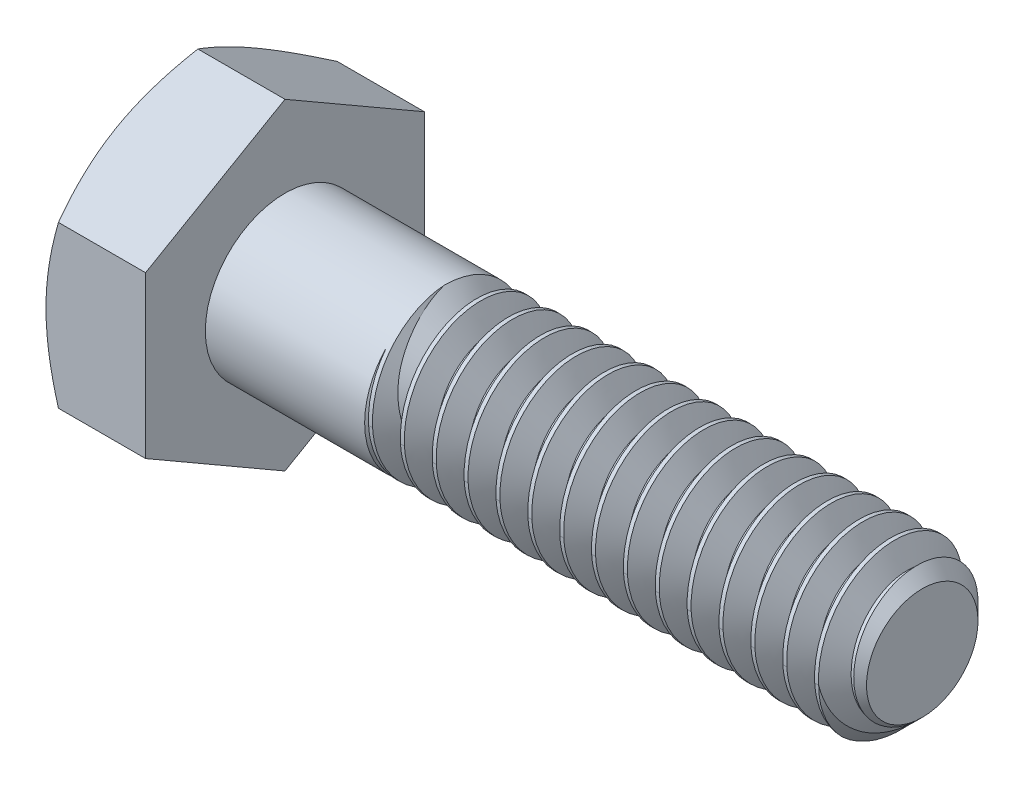
SolidWorks part; units mm, degrees
ref_plane "Front Plane" through (0, 0, 0) normal (0, 0, 1) x (1, 0, 0)
ref_plane "Top Plane" through (0, 0, 0) normal (0, 1, 0) x (1, 0, 0)
ref_plane "Right Plane" through (0, 0, 0) normal (1, 0, 0) x (0, 0, -1)
sketch "Sketch1" plane through (0, 0, 0) normal (0, 0, 1) x (1, 0, 0)
  line L0 (-14.6844, 0) -> (14.6844, 0) construction
  line L1 (14.6844, 3.175) -> (14.6844, -3.175) construction
  line L2 (-10.7156, 5.5562) -> (-10.7156, -5.5562) construction
  line L3 (-14.6844, 5.5562) -> (-14.6844, -5.5562) construction
  point P9 (-10.7156, 0)
  point P10 (10.2394, -3.175)
  dimension "Screw Dia" = 6.35
  dimension "Hex" = 11.1125
  dimension "Head Ht" = 3.9688
  dimension "Screw Lenght" = 25.4
  dimension "D1" = 4.445
ref_plane "Plane2" through (14.6844, 0, 0) normal (1, 0, 0) x (0, 0, -1)
sketch "Sketch5" plane through (14.6844, 0, 0) normal (1, 0, 0) x (0, 0, -1)
  circle A0 centre (0, 0) radius 3.175
extrude "Boss-Extrude3" add sketch "Sketch5" against normal up to vertex (25.4 mm away) up to point (-10.7156, 0, 0)
sketch "Sketch9" plane through (14.6844, 0, 0) normal (1, 0, 0) x (0, 0, -1)
  circle A1 centre (0, 0) radius 3.175
  circle A2 centre (0, 0) radius 3.175
  dimension "D1" = 0
curve "Helix/Spiral1" pitch 1.27 height 26.67 turns 21 parameters "Pitch"=1.27
chamfer "Chamfer1" distance 0.9525 angle 45 1 edges at (14.6844, 0, -3.175)
sketch "Sketch10" plane through (0, 0, 0) normal (0, 0, 1) x (1, 0, 0)
  line L0 (14.6844, 3.175) -> (15.1606, 2.3501)
  line L1 (15.1606, 2.3501) -> (15.3194, 2.3501)
  line L2 (15.3194, 2.3501) -> (15.7956, 3.175)
  line L3 (14.6844, 3.175) -> (15.7956, 3.175)
  line L4 (15.24, 3.175) -> (15.24, 2.3501) construction
  line L5 (14.9225, 2.7626) -> (15.5575, 2.7626) construction
  dimension "D1" = 60
  dimension "D2" = 0.1588
  dimension "D3" = 0.635
sweep "Cut-Sweep1" cut profiles "Sketch10" path "Helix/Spiral1" align with end faces yes
sketch "Sketch11" plane through (0, 0, 0) normal (0, 0, 1) x (1, 0, 0)
  line L0 (-10.7156, 3.175) -> (-10.7156, 0)
  line L1 (-10.7156, 0) -> (-1.1906, 0)
  line L3 (-1.1906, 0) -> (-4.3656, 3.175)
  line L4 (-10.7156, 3.175) -> (-4.3656, 3.175)
  dimension "D1" = 45
  dimension "MIn Thread" = 19.05
revolve "Revolve1" add sketch "Sketch11" angle 360 about L1
sketch "Sketch6" plane through (-10.7156, 0, 0) normal (-1, 0, 0) x (0, 0, 1)
  line L0 (0, 5.5562) -> (0, -5.5562) construction
  line L1 (5.5562, 3.2079) -> (0, 6.4158)
  line L2 (0, 6.4158) -> (-5.5563, 3.2079)
  line L3 (-5.5563, 3.2079) -> (-5.5562, -3.2079)
  line L4 (-5.5562, -3.2079) -> (0, -6.4158)
  line L5 (0, -6.4158) -> (5.5563, -3.2079)
  line L6 (5.5563, -3.2079) -> (5.5562, 3.2079)
  circle A0 centre (0, 0) radius 5.5562 construction
extrude "Boss-Extrude4" add sketch "Sketch6" along normal up to vertex (3.9688 mm away) up to point (-14.6844, -5.5562, 0)
sketch "Sketch7" plane through (-14.6844, 0, 0) normal (-1, 0, 0) x (0, 0, 1)
  circle A0 centre (0, 0) radius 5.5562 construction
  circle A1 centre (0, 0) radius 5.5562
sketch "Sketch8" plane through (-14.6844, 0, 0) normal (-1, 0, 0) x (0, 0, 1)
  circle A0 centre (0, 0) radius 5.5562 construction
  circle A1 centre (0, 0) radius 5.5562
extrude "Cut-Extrude3" cut sketch "Sketch8" against normal through all draft 60 flip side to cut
sketch "Sketch12" plane through (-14.6844, 0, 0) normal (-1, 0, 0) x (0, 0, 1)
  line L0 (0, 4.2783) -> (0, 2.3892) construction
  line L1 (0.1667, 4.2783) -> (0.1667, 2.3892)
  line L2 (-0.1667, 4.2783) -> (-0.1667, 2.3892)
  line L3 (0, 3.175) -> (0, -3.175) construction
  arc A0 (0.1667, 4.2783) -> (-0.1667, 4.2783) centre (0, 4.2783) ccw
  arc A1 (-0.1667, 2.3892) -> (0.1667, 2.3892) centre (0, 2.3892) ccw
  circle A3 centre (0, 0) radius 2.2225 construction
  circle A4 centre (0, 0) radius 4.445 construction
  point P2 (0, 3.3337)
  dimension "D1" = 4.445
  dimension "D3" = 8.89
  dimension "D2" = 0.3334
extrude "Cut-Extrude4" cut sketch "Sketch12" against normal blind 0.254
pattern_circular "CirPattern1" count 3 over 360 about axis through (0, 0, 0) along (1, 0, 0) of "Cut-Extrude4"
equation "\"D2@Sketch10\" = \"Pitch@Helix/Spiral1\"*.125"
equation "\"D3@Sketch10\" = \"Pitch@Helix/Spiral1\"*.5"
equation "\"D3@Helix/Spiral1\" = \"Screw Lenght@Sketch1\"+\"Pitch@Helix/Spiral1\""
equation "\"D1@Chamfer1\" = \"Pitch@Helix/Spiral1\"*.75"
equation "\"D1@Sketch12\" = \"Hex@Sketch1\"*.4"
equation "\"D3@Sketch12\" = \"Hex@Sketch1\"*.8"
equation "\"D2@Sketch12\" = \"Hex@Sketch1\"*.03"
equation "\"D1@Sketch1\" = \"Pitch@Helix/Spiral1\"*3.5"
